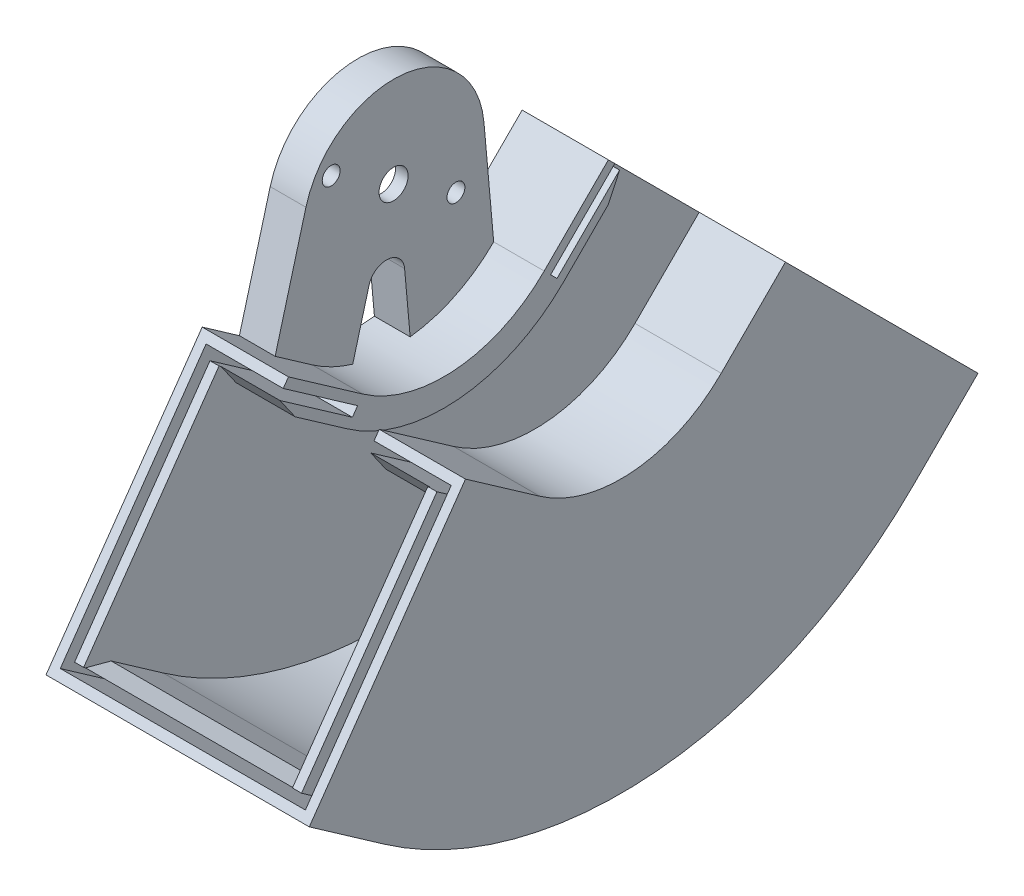
SolidWorks part; units mm, degrees
ref_plane "Front Plane" through (0, 0, 0) normal (0, 0, 1) x (1, 0, 0)
ref_plane "Top Plane" through (0, 0, 0) normal (0, 1, 0) x (1, 0, 0)
ref_plane "Right Plane" through (0, 0, 0) normal (1, 0, 0) x (0, 0, -1)
sketch "Sketch3" plane through (0, 0, 0) normal (1, 0, 0) x (0, 0, -1)
  line L0 (-22.7274, -32.4581) -> (-62.0633, -88.6355)
  line L1 (28.0184, -28.0184) -> (76.5118, -76.5118)
  line L2 (-22.7274, -32.4581) -> (0, 0) construction
  line L3 (0, 0) -> (28.0184, -28.0184) construction
  line L4 (0, 40.513) -> (0, -40.513) construction
  line L5 (-62.0633, -88.6355) -> (-66.4339, -94.8775)
  line L6 (76.5118, -76.5118) -> (81.8999, -81.8999)
  arc A2 (-62.0633, -88.6355) -> (76.5118, -76.5118) centre (0, 0) ccw
  arc A4 (-27.098, -38.7) -> (33.4066, -33.4066) centre (0, 0) ccw
  arc A5 (-22.7274, -32.4581) -> (28.0184, -28.0184) centre (0, 0) ccw
  arc A6 (-66.4339, -94.8775) -> (81.8999, -81.8999) centre (0, 0) ccw
  dimension "D1" = 216.408
  dimension "D2" = 135
  dimension "D3" = 94.488
  dimension "D4" = 7.62
  dimension "D6" = 7.62
  dimension "D5" = 80
extrude "Base extrude" add sketch "Sketch3" along normal blind 58.42 contours L5 A6 L6 A2 | A5 L0 A4 L1 region at (0, -39.9408, -3.4944) region at (0, -109.321, -9.5643)
sketch "Sketch4" plane through (58.42, 0, 0) normal (1, 0, 0) x (0, 0, -1)
  line L0 (-66.4339, -94.8775) -> (-22.7274, -32.4581)
  line L1 (28.0184, -28.0184) -> (81.8999, -81.8999)
  arc A0 (-22.7274, -32.4581) -> (28.0184, -28.0184) centre (0, 0) ccw
  arc A1 (-22.7274, -32.4581) -> (28.0184, -28.0184) centre (0, 0) ccw construction
  arc A2 (-66.4339, -94.8775) -> (81.8999, -81.8999) centre (0, 0) ccw
  arc A3 (-66.4339, -94.8775) -> (81.8999, -81.8999) centre (0, 0) ccw construction
  arc M1 (28.0184, -28.0184) -> (-22.7274, -32.4581) centre (0, 0) cw
  line M2 (-22.7274, -32.4581) -> (-27.098, -38.7)
  arc M3 (-27.098, -38.7) -> (33.4066, -33.4066) centre (0, 0) ccw
  line M4 (33.4066, -33.4066) -> (28.0184, -28.0184)
extrude "Outer wall" add sketch "Sketch4" along normal blind 7.62 contours L0 A2 L1 M3 | M4 M1 M2 M3 region at (58.42, -79.1939, -6.9286) region at (58.42, -39.9408, -3.4944)
ref_plane "Midplane" through (29.21, 0, 0) normal (-1, 0, 0) x (0, 0, 1)
mirror "Mirror1" about plane through (29.21, 0, 0) normal (-1, 0, 0) of "Outer wall"
sketch "Sketch6" plane through (0, 0, 0) normal (0, 0.5736, 0.8192) x (1, 0, 0)
  line L27 (-5.08, -42.164) -> (63.5, -42.164)
  line L28 (-5.08, -42.164) -> (-5.08, -113.284)
  line L29 (-5.08, -113.284) -> (63.5, -113.284)
  line L30 (63.5, -42.164) -> (63.5, -113.284)
  line L31 (-2.54, -44.704) -> (60.96, -44.704)
  line L32 (-2.54, -44.704) -> (-2.54, -110.744)
  line L33 (-2.54, -110.744) -> (60.96, -110.744)
  line L34 (60.96, -44.704) -> (60.96, -110.744)
  line L35 (58.42, -47.244) -> (0, -47.244) construction
  line L36 (0, -108.204) -> (0, -18.7894) construction
  line L37 (58.42, -18.7894) -> (58.42, -108.204) construction
  line L38 (58.42, -108.204) -> (0, -108.204) construction
  line L40 (0, -47.244) -> (58.42, -47.244)
  line L41 (0, -47.244) -> (0, -108.204)
  line L42 (0, -108.204) -> (58.42, -108.204)
  line L43 (58.42, -47.244) -> (58.42, -108.204)
  line L44 (-7.62, -39.624) -> (66.04, -39.624)
  line L45 (-7.62, -39.624) -> (-7.62, -115.824)
  line L46 (-7.62, -115.824) -> (66.04, -115.824)
  line L47 (66.04, -39.624) -> (66.04, -115.824)
  line M21 (-7.62, -39.624) -> (-7.62, -115.824)
  line M22 (-7.62, -115.824) -> (66.04, -115.824)
  line M23 (66.04, -115.824) -> (66.04, -39.624)
  line M24 (66.04, -39.624) -> (-7.62, -39.624)
  line M25 (58.42, -108.204) -> (0, -108.204)
  line M26 (0, -108.204) -> (0, -47.244)
  line M27 (0, -47.244) -> (58.42, -47.244)
  line M28 (58.42, -47.244) -> (58.42, -108.204)
  dimension "D1" = 2.54
  dimension "D2" = 2.54
  dimension "D3" = 2.54
  dimension "D4" = 2.54
  dimension "D5" = 2.54
  dimension "D6" = 2.54
  dimension "D7" = 2.54
  dimension "D8" = 2.54
extrude "Endcap 1" add sketch "Sketch6" along normal blind 25.4 contours L27 L30 L29 L28 M24 M21 M22 M23 | L34 L31 L32 L33 M28 M25 M26 M27 region at (29.21, -37.3698, 26.1667) region at (29.21, -33.3262, 23.3353)
sketch "Sketch7" plane through (0, 0, 0) normal (0, 0.7071, -0.7071) x (1, 0, 0)
  line L0 (-5.08, 113.284) -> (63.5, 113.284)
  line L1 (-5.08, 113.284) -> (-5.08, 42.164)
  line L2 (-5.08, 42.164) -> (63.5, 42.164)
  line L3 (63.5, 113.284) -> (63.5, 42.164)
  line L4 (-2.54, 110.744) -> (60.96, 110.744)
  line L5 (-2.54, 110.744) -> (-2.54, 44.704)
  line L6 (-2.54, 44.704) -> (60.96, 44.704)
  line L7 (60.96, 110.744) -> (60.96, 44.704)
  line L8 (0, 108.204) -> (58.42, 108.204)
  line L9 (0, 108.204) -> (0, 47.244)
  line L10 (0, 47.244) -> (58.42, 47.244)
  line L11 (58.42, 108.204) -> (58.42, 47.244)
  line L12 (-7.62, 115.824) -> (66.04, 115.824)
  line L13 (-7.62, 115.824) -> (-7.62, 39.624)
  line L14 (-7.62, 39.624) -> (66.04, 39.624)
  line L15 (66.04, 115.824) -> (66.04, 39.624)
  line L16 (58.42, 108.204) -> (0, 108.204) construction
  line L17 (58.42, 47.244) -> (58.42, 108.204) construction
  line L18 (66.04, 115.824) -> (-7.62, 115.824) construction
  line L19 (66.04, 39.624) -> (66.04, 115.824) construction
  line L20 (-7.62, 39.624) -> (-7.62, 115.824) construction
  line L21 (66.04, 39.624) -> (-7.62, 39.624) construction
  line M17 (66.04, 115.824) -> (-7.62, 115.824)
  line M18 (-7.62, 115.824) -> (-7.62, 39.624)
  line M19 (-7.62, 39.624) -> (66.04, 39.624)
  line M20 (66.04, 39.624) -> (66.04, 115.824)
  line M21 (0, 47.244) -> (0, 108.204)
  line M22 (0, 108.204) -> (58.42, 108.204)
  line M23 (58.42, 108.204) -> (58.42, 47.244)
  line M24 (58.42, 47.244) -> (0, 47.244)
  dimension "D1" = 2.54
  dimension "D2" = 2.54
  dimension "D3" = 2.54
  dimension "D4" = 2.54
  dimension "D5" = 2.54
  dimension "D6" = 2.54
  dimension "D7" = 2.54
  dimension "D8" = 2.54
extrude "Endcap 2" add sketch "Sketch7" along normal blind 25.4 contours L0 L3 L2 L1 M20 M17 M18 M19 | L7 L4 L5 L6 M24 M21 M22 M23 region at (29.21, -77.66, -77.66) region at (29.21, -81.1505, -81.1505)
chamfer "Internal Chamfer" distance 7.62 angle 20 4 edges at (29.21, -74.0667, 82.8697) (29.21, -24.1312, 47.9045) (29.21, -58.5513, -94.4723) (29.21, -15.446, -51.3671) first distance on face at (29.21, -81.3511, 72.4665) first distance on face at (29.21, -31.4156, 37.5013) first distance on face at (29.21, -67.5315, -85.492) first distance on face at (29.21, -24.4263, -42.3868)
ref_plane "Plane2" through (0, -13.9736, -1.2225) normal (0, -0.9962, -0.0872) x (-1, 0, 0)
sketch "Sketch10" plane through (0, -13.9736, -1.2225) normal (0, -0.9962, -0.0872) x (-1, 0, 0)
  line L0 (-66.04, 93.9078) -> (7.62, 93.9078) construction
  line L1 (-16.51, 95.5358) -> (-41.91, 95.5358)
  line L2 (-16.51, 95.5358) -> (-16.51, -82.1857)
  line L3 (-16.51, -82.1857) -> (-41.91, -82.1857)
  line L4 (-41.91, 95.5358) -> (-41.91, -82.1857)
  point P4 (-29.21, 93.9078)
  point P5 (-29.21, 95.5358)
  dimension "D1" = 25.4
extrude "Flywheel Hole" cut sketch "Sketch10" along normal up to next
sketch "Sketch11" plane through (-7.62, 0, 0) normal (-1, 0, 0) x (0, 0, 1)
  line L0 (-25.2982, 2.2719) -> (-28.0184, -28.0184)
  line L4 (-3.0897, -22.02) -> (-4.6461, -39.3507)
  line L5 (6.8734, -21.1467) -> (11.421, -37.9424)
  line L6 (-17.454, -10.7521) -> (17.454, 10.7521) construction
  line L7 (24.5172, 6.6383) -> (33.1306, -25.1737)
  line L8 (43.5339, -17.8892) -> (22.7274, -32.4581) construction
  line L10 (1.5263, -17.4138) -> (-2.2178, 25.303) construction
  line L11 (22.7274, -32.4581) -> (43.5339, -17.8892)
  line L12 (22.7274, -32.4581) -> (33.1306, -25.1737)
  arc A1 (-28.0184, -28.0184) -> (22.7274, -32.4581) centre (0, 0) ccw construction
  circle A3 centre (0, 0) radius 4.064
  arc A4 (24.5172, 6.6383) -> (-25.2982, 2.2719) centre (0, 0) ccw
  circle A6 centre (-17.454, -10.7521) radius 2.5
  circle A7 centre (17.454, 10.7521) radius 2.5
  arc A8 (-3.0897, -22.02) -> (6.8734, -21.1467) centre (1.9699, -22.4744) cw
  arc A11 (11.421, -37.9424) -> (22.7274, -32.4581) centre (0, 0) ccw
  arc A12 (-28.0184, -28.0184) -> (22.7274, -32.4581) centre (0, 0) ccw
  arc A13 (-28.0184, -28.0184) -> (-4.6461, -39.3507) centre (0, 0) ccw
  point P22 (0, 0)
  dimension "D3" = 8.128
  dimension "D2" = 25.4
  dimension "D1" = 5
  dimension "D5" = 5.08
  dimension "D4" = 41
  dimension "D6" = 0
extrude "Flywheel holder" add sketch "Sketch11" against normal blind 10
sketch "Sketch12" plane through (-7.62, 0, 0) normal (-1, 0, 0) x (0, 0, 1)
  circle A0 centre (0, 0) radius 17
  dimension "D1" = 34
extrude "Motor insert" cut sketch "Sketch12" against normal blind 6.5
